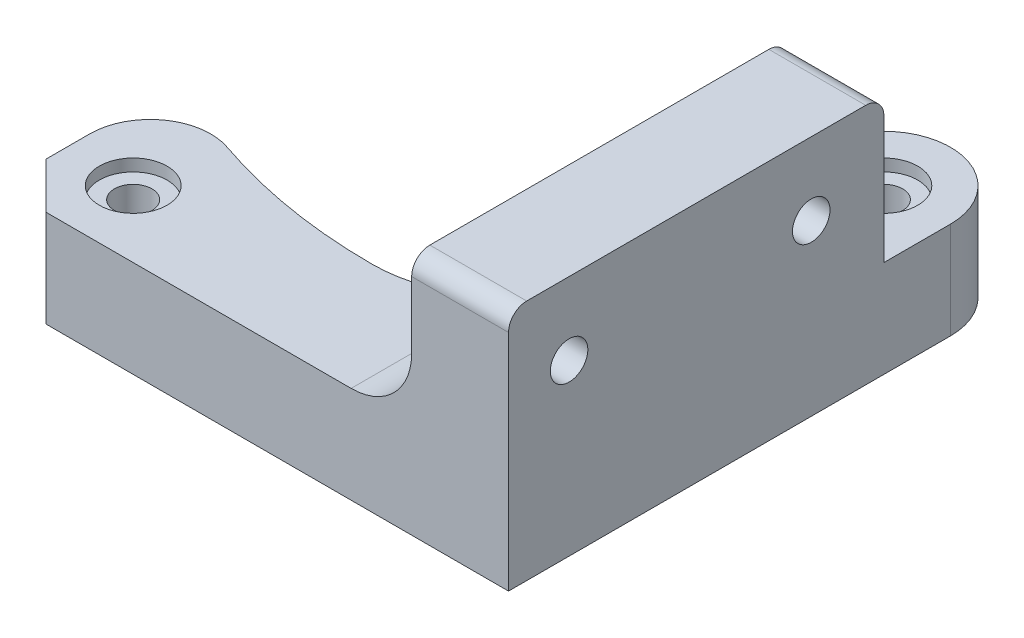
SolidWorks part; units mm, degrees
ref_plane "Alzado" through (0, 0, 0) normal (0, 0, 1) x (1, 0, 0)
ref_plane "Planta" through (0, 0, 0) normal (0, 1, 0) x (1, 0, 0)
ref_plane "Vista lateral" through (0, 0, 0) normal (1, 0, 0) x (0, 0, -1)
sketch "Croquis1" plane through (0, 0, 0) normal (0, 1, 0) x (1, 0, 0)
  line L0 (21, 42) -> (21, 0) construction
  line L1 (0, 0) -> (42, 0)
  line L2 (0, 0) -> (0, 42) construction
  line L3 (0, 42) -> (42, 42) construction
  line L4 (42, 0) -> (42, 36.5)
  line L5 (0, 15.0394) -> (0, 0)
  circle A0 centre (36.5, 36.5) radius 1.55
  circle A1 centre (5.5, 5.5) radius 1.55
  arc A2 (21, 9.75) -> (21, 32.25) centre (21, 21) ccw
  arc A3 (0, 15.0394) -> (21, 9.75) centre (20.9082, 53.7172) ccw
  arc A4 (42, 36.5) -> (31.1961, 37.9557) centre (36.5, 36.5) ccw
  arc A5 (21, 32.25) -> (31.1961, 37.9557) centre (20.567, 44.987) ccw
  dimension "D3" = 3.1
  dimension "D4" = 5.5
  dimension "D8" = 22.5
  dimension "D1" = 42
  dimension "D2" = 42
  dimension "D5" = 5.5
  dimension "D6" = 5.5
  dimension "D7" = 5.5
extrude "Saliente-Extruir2" add sketch "Croquis1" along normal blind 8
fillet "Redondeo1" radius 8 1 edges at (21, 4, -32.25)
fillet "Redondeo2" radius 5 1 edges at (0, 4, -15.0394)
sketch "Croquis2" plane through (0, 8, 0) normal (0, 1, 0) x (1, 0, 0)
  circle A0 centre (36.5, 36.5) radius 2.8
  circle A1 centre (5.5, 5.5) radius 2.8
  dimension "D1" = 5.6
extrude "Cortar-Extruir1" cut sketch "Croquis2" against normal blind 1
sketch "Croquis3" plane through (0, 8, 0) normal (0, 1, 0) x (1, 0, 0)
  line L1 (42, 0) -> (34, 0)
  line L2 (42, 0) -> (42, 31)
  line L3 (42, 31) -> (34, 31)
  line L4 (34, 0) -> (34, 31)
  dimension "D1" = 8
  dimension "D2" = 31
extrude "Saliente-Extruir3" add sketch "Croquis3" along normal blind 12
sketch "Croquis4" plane through (34, 0, 0) normal (-1, 0, 0) x (0, 0, 1)
  line L0 (-31, 14) -> (0, 14) construction
  line L1 (-31, 20) -> (-31, 8) construction
  line L2 (0, 20) -> (0, 8) construction
  circle A0 centre (-25, 14) radius 1.55
  circle A1 centre (-5, 14) radius 1.55
  dimension "D1" = 3.1
  dimension "D3" = 5
  dimension "D2" = 20
extrude "Cortar-Extruir2" cut sketch "Croquis4" against normal up to surface (8 mm away) up to face at (42, 9.3333, -22.5)
sketch "Croquis5" plane through (34, 0, 0) normal (-1, 0, 0) x (0, 0, 1)
  line L1 (-25, 17.3486) -> (-27.9, 15.6743)
  line L2 (-27.9, 15.6743) -> (-27.9, 12.3257)
  line L3 (-27.9, 12.3257) -> (-25, 10.6514)
  line L4 (-25, 10.6514) -> (-22.1, 12.3257)
  line L5 (-22.1, 12.3257) -> (-22.1, 15.6743)
  line L6 (-22.1, 15.6743) -> (-25, 17.3486)
  line L7 (-5, 17.3486) -> (-7.9, 15.6743)
  line L8 (-7.9, 15.6743) -> (-7.9, 12.3257)
  line L9 (-7.9, 12.3257) -> (-5, 10.6514)
  line L10 (-5, 10.6514) -> (-2.1, 12.3257)
  line L11 (-2.1, 12.3257) -> (-2.1, 15.6743)
  line L12 (-2.1, 15.6743) -> (-5, 17.3486)
  circle A0 centre (-25, 14) radius 2.9 construction
  circle A1 centre (-5, 14) radius 2.9 construction
  point P10 (-3.55, 11.4885)
  dimension "D1" = 5.8
  dimension "D2" = 5.8
extrude "Cortar-Extruir3" cut sketch "Croquis5" against normal blind 2.5 contours L1 L2 L3 L4 L5 L6 | L7 L8 L9 L10 L11 L12
fillet "Redondeo3" radius 5 1 edges at (34, 8, -15.5)
fillet "Redondeo4" radius 1.5 2 edges at (38, 20, 0) (38, 20, -31)
chamfer "Chaflán1" distance 3.8 angle 45 1 edges at (0, 4, 0)
